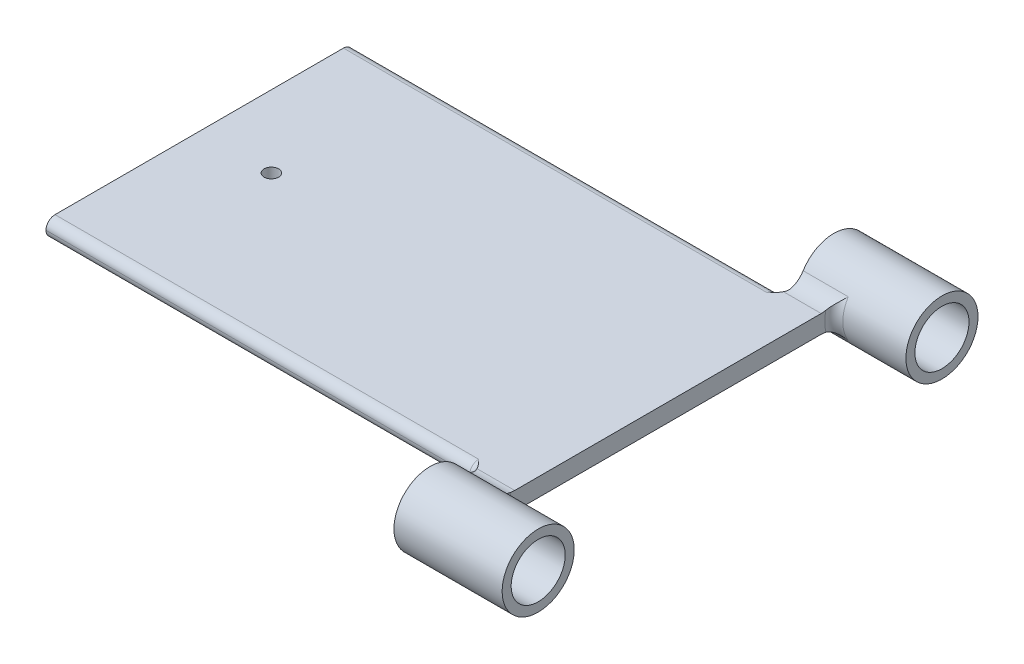
SolidWorks part; units mm, degrees
note: The reader was unsure of these and kept them because the rebuilt part matched: shared geometry of "Sketch5<3>".
ref_plane "Front Plane" through (0, 0, 0) normal (0, 0, 1) x (1, 0, 0)
ref_plane "Top Plane" through (0, 0, 0) normal (0, 1, 0) x (1, 0, 0)
ref_plane "Right Plane" through (0, 0, 0) normal (1, 0, 0) x (0, 0, -1)
sketch "Sketch1" plane through (0, 0, 0) normal (1, 0, 0) x (0, 0, -1)
  line L1 (0, 0) -> (-107.95, 0)
  line L2 (0, 0) -> (0, 6.35)
  line L3 (0, 6.35) -> (-107.95, 6.35)
  line L4 (-107.95, 0) -> (-107.95, 6.35)
  dimension "D1" = 107.95
  dimension "D2" = 6.35
extrude "Boss-Extrude2" add sketch "Sketch1" along normal blind 165.1
ref_plane "Plane2" through (0, 0, 53.975) normal (0, 0, 1) x (1, 0, 0)
sketch "Sketch5" plane through (165.1, 0, 0) normal (1, 0, 0) x (0, 0, -1)
  line L0 (0, 0) -> (-107.95, 0) construction
  line L1 (0, 6.35) -> (-107.95, 6.35) construction
  line L2 (0, 0) -> (0, 6.35)
  arc A0 (0, 0) -> (6.35, -3.5296) centre (0, -7.4768) cw
  arc A1 (0, 6.35) -> (6.35, 9.8796) centre (0, 13.8268) ccw
  circle A2 centre (17.136, 3.175) radius 12.7
  line M1 (0, 0) -> (0, 6.35)
  dimension "D1" = 25.4
  dimension "D2" = 6.35
extrude "Boss-Extrude4" add sketch "Sketch5" against normal blind 12.7 contours A2 | A2 A1 A0 M1
extrude "Boss-Extrude5" add sketch "Sketch5<3>" along normal blind 25.4 contours A2
sketch "Sketch5<3>" plane through (165.1, 0, 0) normal (1, 0, 0) x (0, 0, -1) same geometry as "Sketch5"
sketch "Sketch6" plane through (190.5, 0, 0) normal (1, 0, 0) x (0, 0, -1)
  circle A0 centre (17.136, 3.175) radius 9.525
  dimension "D1" = 19.05
extrude "Cut-Extrude3" cut sketch "Sketch6" against normal blind 15.875
sketch "Sketch7" plane through (152.4, 0, 0) normal (-1, 0, 0) x (0, 0, 1)
  circle A0 centre (-17.136, 3.175) radius 9.525
  dimension "D1" = 19.05
extrude "Cut-Extrude4" cut sketch "Sketch7" against normal blind 15.875
sketch "Sketch8" plane through (174.625, 0, 0) normal (1, 0, 0) x (0, 0, -1)
  circle A0 centre (17.136, 3.175) radius 3.175
  dimension "D1" = 6.35
extrude "Cut-Extrude5" cut sketch "Sketch8" against normal up to next
mirror "Mirror5" about plane through (0, 0, 53.975) normal (0, 0, 1) of "Cut-Extrude5", "Cut-Extrude4", "Boss-Extrude5", "Cut-Extrude3", "Boss-Extrude4"
fillet "Fillet17" radius 3.175 4 edges
fillet "Fillet18" radius 3.175 6 edges at (152.4, 0.9299, 107.0201) (165.1, 3.175, 112.386) (152.4, 5.4201, 107.0201) (152.4, 5.4201, 0.9299) (152.4, 0.9299, 0.9299)
hole_wizard "1/4-20 Tapped Hole1" positions "3DSketch4" profile "Sketch9" tap size "1/4-20" standard "ANSI Inch" end condition through all
sketch3d "3DSketch4"
  line L0 (0, 0, 104.775) -> (0, 0, 3.175) construction
  line L7 (0, 0, 53.975) -> (165.1, 0, 53.975) construction
  line L8 (165.1, 0, 107.95) -> (165.1, 0, 0) construction
  point P0 (25.4, 0, 53.975)
  dimension "D1" = 25.4
sketch "Sketch9" plane through (25.4, 0, 53.975) normal (1, 0, 0) x (0, 0, -1)
  line L0 (0, 0) -> (0, 15.875)
  line L1 (0, 15.875) -> (2.5527, 15.875)
  line L2 (2.5527, 15.875) -> (2.5527, 0)
  line L5 (2.5527, 0) -> (0, 0)
  line L11 (0, -6.35) -> (0, 107.95) construction
  dimension "Thru Tap Drill Dia." = 5.1054
  dimension "Thru Tap Drill Depth" = 15.875
cosmetic thread "Hole Thread1" parameters "D2"=6.35
